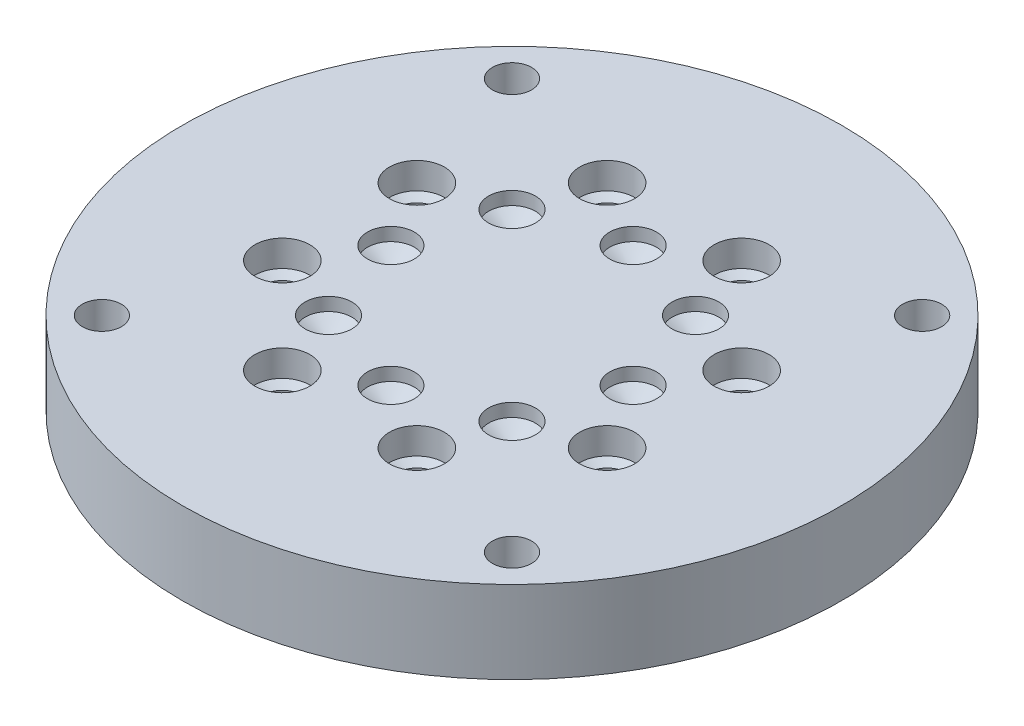
SolidWorks part; units mm, degrees
material "Copper"
ref_plane "Front Plane" through (0, 0, 0) normal (0, 0, 1) x (1, 0, 0)
ref_plane "Top Plane" through (0, 0, 0) normal (0, 1, 0) x (1, 0, 0)
ref_plane "Right Plane" through (0, 0, 0) normal (1, 0, 0) x (0, 0, -1)
ref_axis "Y Axis" through (0, 0.1588, 0) along (0, -1, 0)
sketch "outer" plane through (0, 0, 0) normal (0, 1, 0) x (1, 0, 0)
  circle A0 centre (0, 0) radius 19.05
  dimension "D1" = 38.1
extrude "Body" add sketch "outer" against normal blind 4.7625
sketch "Screw Position" plane through (0, 0, 0) normal (0, 1, 0) x (1, 0, 0)
  point P0 (-11.8539, 11.8539)
  dimension "D1" = 16.764
hole_wizard "#4-40 Tapped Hole" positions "Sketch12" profile "Sketch13" tap size "#4-40" standard "ANSI Inch" end condition through all
sketch "Sketch12" plane through (0, 0, 0) normal (0, 1, 0) x (1, 0, 0)
  point P0 (-11.8539, 11.8539)
sketch "Sketch13" plane through (-11.8539, 0, -11.8539) normal (1, 0, 0) x (0, 0, 1)
  line L0 (0, 0) -> (0, 4.7625)
  line L1 (0, 4.7625) -> (1.1303, 4.7625)
  line L2 (1.1303, 4.7625) -> (1.1303, 0)
  line L5 (1.1303, 0) -> (0, 0)
  line L11 (0, -6.35) -> (0, 107.95) construction
  dimension "Thru Tap Drill Dia." = 2.2606
  dimension "Thru Tap Drill Depth" = 4.7625
cosmetic thread "Hole Thread3" parameters "D2"=2.8448
pattern_circular "Screw Holes" count 4 over 360 about axis through (0, 0.1588, 0) along (0, -1, 0) of "#4-40 Tapped Hole"
sketch "inner" plane through (0, 0, 0) normal (0, 1, 0) x (1, 0, 0)
  circle A0 centre (0, 0) radius 11.938
  dimension "D1" = 23.876
sketch "IO Hole Location" plane through (0, 0, 0) normal (0, 1, 0) x (1, 0, 0)
  point P0 (-3.8881, 9.3866)
  dimension "D1" = 10.16
hole_wizard "#43 (0.089) Diameter Hole1" positions "Sketch36" profile "Sketch37" hole size "#43" standard "ANSI Inch" end condition through all
sketch "Sketch36" plane through (0, 0, 0) normal (0, 1, 0) x (1, 0, 0)
  point P0 (-3.8881, 9.3866)
sketch "Sketch37" plane through (-3.8881, 0, -9.3866) normal (1, 0, 0) x (0, 0, 1)
  line L0 (0, 0) -> (0, 4.7625)
  line L1 (0, 4.7625) -> (1.1303, 4.7625)
  line L2 (1.1303, 4.7625) -> (1.1303, 0)
  line L5 (1.1303, 0) -> (0, 0)
  line L11 (0, -6.35) -> (0, 107.95) construction
  dimension "Thru Hole Dia." = 2.2606
  dimension "Thru Hole Depth" = 4.7625
hole_wizard "1/8 (0.125) Diameter Hole1" positions "Sketch38" profile "Sketch40" hole size "1/8" standard "ANSI Inch"
sketch "Sketch38" plane through (0, 0, 0) normal (0, 1, 0) x (1, 0, 0)
  point P0 (-3.8881, 9.3866)
sketch "Sketch40" plane through (-3.8881, 0, -9.3866) normal (1, 0, 0) x (0, 0, 1)
  line L0 (0, 0) -> (0, 2.4779)
  line L1 (0, 2.4779) -> (1.5875, 1.524)
  line L2 (1.5875, 1.524) -> (1.5875, 0)
  line L5 (1.5875, 0) -> (0, 0)
  line L10 (0, 2.4779) -> (-1.5875, 1.524) construction
  line L11 (0, -6.35) -> (0, 107.95) construction
  dimension "Hole Dia." = 3.175
  dimension "Hole Depth" = 1.524
  dimension "Drill Angle" = 118
hole_wizard "1/8 (0.125) Diameter Hole2" positions "Sketch41" profile "Sketch42" hole size "1/8" standard "ANSI Inch"
sketch "Sketch41" plane through (0, -4.7625, 0) normal (0, -1, 0) x (-1, 0, 0)
  point P0 (3.8881, 9.3866)
sketch "Sketch42" plane through (-3.8881, -4.7625, -9.3866) normal (1, 0, 0) x (0, 0, -1)
  line L0 (0, 0) -> (0, 2.4779)
  line L1 (0, 2.4779) -> (1.5875, 1.524)
  line L2 (1.5875, 1.524) -> (1.5875, 0)
  line L5 (1.5875, 0) -> (0, 0)
  line L10 (0, 2.4779) -> (-1.5875, 1.524) construction
  line L11 (0, -6.35) -> (0, 107.95) construction
  dimension "Hole Dia." = 3.175
  dimension "Hole Depth" = 1.524
  dimension "Drill Angle" = 118
pattern_circular "IO Holes Pattern" count 8 over 360 about axis through (0, 0.1588, 0) along (0, -1, 0) of "#43 (0.089) Diameter Hole1", "1/8 (0.125) Diameter Hole1", "1/8 (0.125) Diameter Hole2"
sketch "Post Bottom Location" plane through (0, 0, 0) normal (0, 1, 0) x (1, 0, 0)
  point P0 (0, 7)
  point P1 (-5.3033, 5.3033)
  dimension "D1" = 7
  dimension "D2" = 7.5
hole_wizard "#36 (0.1065) Diameter Hole1" positions "Sketch44" profile "Sketch45" hole size "#36" standard "ANSI Inch"
sketch "Sketch44" plane through (0, 0, 0) normal (0, 1, 0) x (1, 0, 0)
  point P0 (0, 7)
  point P3 (-5.3033, 5.3033)
sketch "Sketch45" plane through (0, 0, -7) normal (1, 0, 0) x (0, 0, 1)
  line L0 (0, 0) -> (0, 1.5747)
  line L1 (0, 1.5747) -> (1.3525, 0.762)
  line L2 (1.3525, 0.762) -> (1.3525, 0)
  line L5 (1.3525, 0) -> (0, 0)
  line L10 (0, 1.5747) -> (-1.3525, 0.762) construction
  line L11 (0, -6.35) -> (0, 107.95) construction
  dimension "Hole Dia." = 2.7051
  dimension "Hole Depth" = 0.762
  dimension "Drill Angle" = 118
pattern_circular "Post Bottoms" count 4 over 360 about axis through (0, 0.1588, 0) along (0, -1, 0) of "#36 (0.1065) Diameter Hole1"
equation "\"outer_d\"= 3 / 2in"
equation "\"screw_r\"= 0.66in"
equation "\"inner_d\"= 0.940in"
equation "\"bottom_h\"= 3 / 16in"
equation "\"pocket_h\"= 0.060in"
equation "\"screw_inner_r\"= 0.415in"
equation "\"io_r\"= 0.4in"
equation "\"D1@outer\" = \"outer_d\""
equation "\"D1@Body\" = \"bottom_h\""
equation "\"D1@inner\" = \"inner_d\""
equation "\"D1@Screw Position\" = \"screw_r\""
equation "\"D1@IO Hole Location\"=\"io_r\""
equation "\"post_r1\"= 7mm"
equation "\"post_r2\"= 7.5mm"
equation "\"D1@Post Bottom Location\" = \"post_r1\""
equation "\"D2@Post Bottom Location\" = \"post_r2\""
equation "\"post_bottom_h\"= 0.03in"
